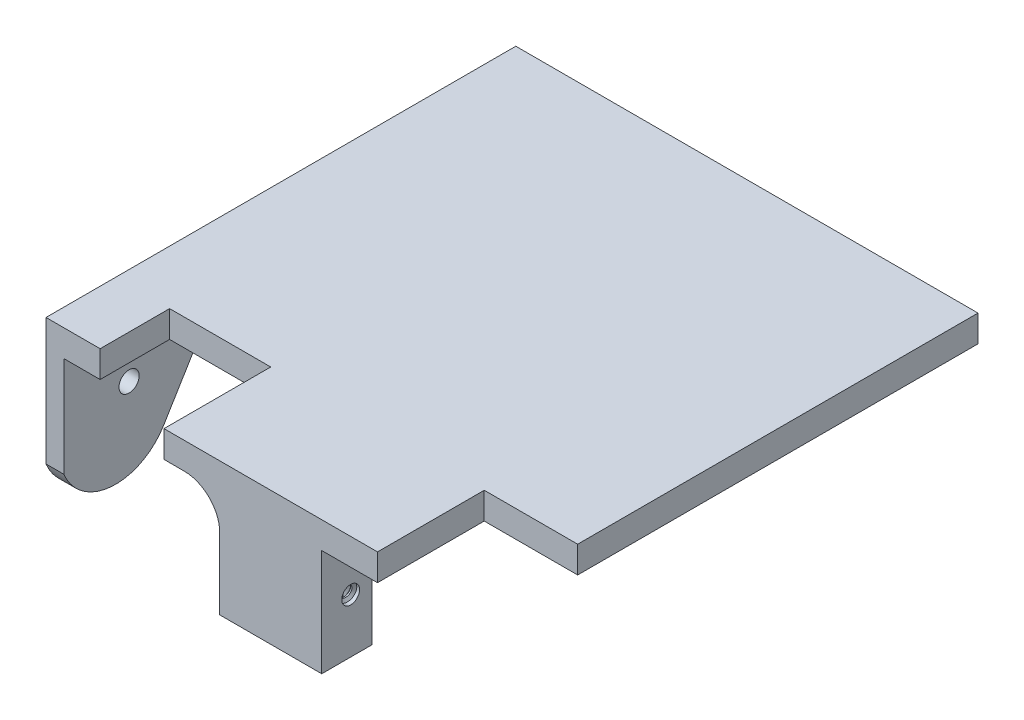
SolidWorks part; units mm, degrees
ref_plane "前视基准面" through (0, 0, 0) normal (0, 0, 1) x (1, 0, 0)
ref_plane "上视基准面" through (0, 0, 0) normal (0, 1, 0) x (1, 0, 0)
ref_plane "右视基准面" through (0, 0, 0) normal (1, 0, 0) x (0, 0, -1)
sketch "草图1" plane through (0, 0, 0) normal (0, 1, 0) x (1, 0, 0)
  line L1 (-23.3681, -22.5) -> (-12, -22.5)
  line L2 (-29.453, -22.5) -> (-29.453, 22.5)
  line L3 (-29.453, 22.5) -> (22.5, 22.5)
  line L4 (22.5, -22.5) -> (22.5, 22.5)
  line L7 (-23.3681, -22.5) -> (-23.3681, -30.3084)
  line L8 (0, -34.5) -> (12, -34.5)
  line L9 (0, -34.5) -> (-12, -34.5)
  line L10 (-12, -34.5) -> (-12, -22.5)
  line L11 (12, -34.5) -> (12, -22.5)
  line L12 (-23.3681, -30.3084) -> (-29.453, -30.3084)
  line L13 (-29.453, -30.3084) -> (-29.453, -22.5)
  line L14 (12, -22.5) -> (22.5, -22.5)
  point P0 (0, 0)
  point P5 (0, 0)
extrude "凸台-拉伸1" add sketch "草图1" against normal blind 3
sketch "草图2" plane through (0, -3, 0) normal (0, -1, 0) x (1, 0, 0)
  line L0 (0, 0) -> (0, 34.5)
  line L5 (-12, 34.5) -> (12, 34.5) construction
  line L7 (5.7336, 28.87) -> (-5.7336, 28.87)
  line L8 (5.7336, 28.87) -> (5.7336, 34.5)
  line L9 (5.7336, 34.5) -> (-5.7336, 34.5)
  line L10 (-5.7336, 28.87) -> (-5.7336, 34.5)
  line L11 (5.7336, 28.87) -> (-5.7336, 34.5) construction
  line L12 (5.7336, 34.5) -> (-5.7336, 28.87) construction
  point P4 (0, 31.685)
  line M8 (12, 34.5) -> (-12, 34.5)
extrude "凸台-拉伸2" add sketch "草图2" along normal blind 12 contours L10 L7 L0 M8 | L7 L8 L0 M8 region at (-2.8668, -3, 31.685) region at (2.8668, -3, 31.685)
fillet "圆角2" radius 4 1 edges at (-5.7336, -3, 31.685)
sketch "草图4" plane through (0, -3, 0) normal (0, -1, 0) x (1, 0, 0)
  line L0 (5.7336, 28.87) -> (-9.7336, 28.87) construction
  line L1 (-2, 28.87) -> (-2, 1.67)
  line L2 (5.7336, 28.87) -> (5.7336, 1.67)
  line L3 (-2, 6.37) -> (5.7336, 6.37)
  line L4 (-9.7336, 28.87) -> (-9.7336, 1.67)
  line L5 (-2, 1.67) -> (-2, -1.2432)
  line L6 (-2, -1.2432) -> (5.7336, -1.2432)
  line L8 (5.7336, -1.2432) -> (5.7336, 1.67)
  line L9 (8.2336, 1.67) -> (5.7336, 1.67) construction
  line L10 (5.7336, 6.37) -> (5.7336, 1.67) construction
  line L11 (5.7336, 6.37) -> (-10.1664, 6.37) construction
  line L12 (-2, -1.2432) -> (-2, 6.37)
  line L13 (5.7336, 6.37) -> (5.7336, -1.2432)
extrude "凸台-拉伸3" add sketch "草图4" along normal blind 12 contours L8 region at (1.8668, -3, 2.5634)
fillet "圆角3" radius 4 1 edges at (-2, -3, 2.5634)
sketch "草图6" plane through (-29.453, 0, 0) normal (-1, 0, 0) x (0, 0, 1)
  line L1 (22.5, -3) -> (34.5, -3) construction
  line L2 (30.3084, -3) -> (30.3084, 0) construction
  line L3 (30.3084, -7) -> (30.3084, -14.2622)
  line L6 (30.3084, -3) -> (30.3084, -7)
  line L7 (19.1009, -15.1363) -> (11.7184, -3)
  line L8 (34.5, -7) -> (28.87, -7) construction
  line L9 (11.7184, -3) -> (30.3084, -3)
  line L10 (-22.5, -3) -> (30.3084, -3) construction
  arc A4 (19.1009, -15.1363) -> (30.3084, -14.2622) centre (24.4834, -11.8621) ccw
  circle A5 centre (22.97, -8.9) radius 1.1324
  dimension "D1" = 4
sketch "草图7" plane through (5.7336, 0, 0) normal (1, 0, 0) x (0, 0, -1)
  circle A0 centre (-3.991, -8.9197) radius 1
extrude "切除-拉伸1" cut sketch "草图7" against normal blind 2
thread "螺纹线1" pitch 0.635 method extrude profile "螺纹线轮廓1" start angle 0, offset 0, length 2, pitch 0.635, diameter 2
ref_plane "基准面1" through (5.7336, -8.9197, 4.991) normal (0, -1, 0) x (0, 0, 1)
sketch "螺纹线轮廓1" plane through (5.7336, -8.9197, 4.991) normal (0, -1, 0) x (0, 0, 1)
  line L0 (0, 0) -> (0, 0.635) construction
  line L11 (0, 0) -> (0, 0.5556)
  line L12 (0, 0.5556) -> (-0.3437, 0.3572)
  line L13 (-0.3437, 0.3572) -> (-0.3437, 0.1984)
  line L15 (-0.3437, 0.1984) -> (0, 0)
  line L17 (-0.3437, 0.2778) -> (0, 0.2778) construction
  point P2 (0, 0)
  dimension "Pitch" = 0.635
  dimension "Profile_Angle" = 60
  dimension "Profile_Land" = 0.1588
  dimension "Profile_Height" = 0.3437
sketch "草图17" plane through (5.7336, 0, 0) normal (1, 0, 0) x (0, 0, -1)
  circle A0 centre (-31.249, -8.9197) radius 1
extrude "切除-拉伸2" cut sketch "草图17" against normal blind 2
thread "螺纹线2" pitch 0.635 method extrude profile "螺纹线轮廓2" start angle 0, offset 0, length 2, pitch 0.635, diameter 2
ref_plane "基准面2" through (5.7336, -8.9197, 32.249) normal (0, -1, 0) x (0, 0, 1)
sketch "螺纹线轮廓2" plane through (5.7336, -8.9197, 32.249) normal (0, -1, 0) x (0, 0, 1)
  line L0 (0, 0) -> (0, 0.635) construction
  line L11 (0, 0) -> (0, 0.5556)
  line L12 (0, 0.5556) -> (-0.3437, 0.3572)
  line L13 (-0.3437, 0.3572) -> (-0.3437, 0.1984)
  line L15 (-0.3437, 0.1984) -> (0, 0)
  line L17 (-0.3437, 0.2778) -> (0, 0.2778) construction
  point P2 (0, 0)
  dimension "Pitch" = 0.635
  dimension "Profile_Angle" = 60
  dimension "Profile_Land" = 0.1588
  dimension "Profile_Height" = 0.3437
extrude "凸台-拉伸4" add sketch "草图6" against normal blind 2
